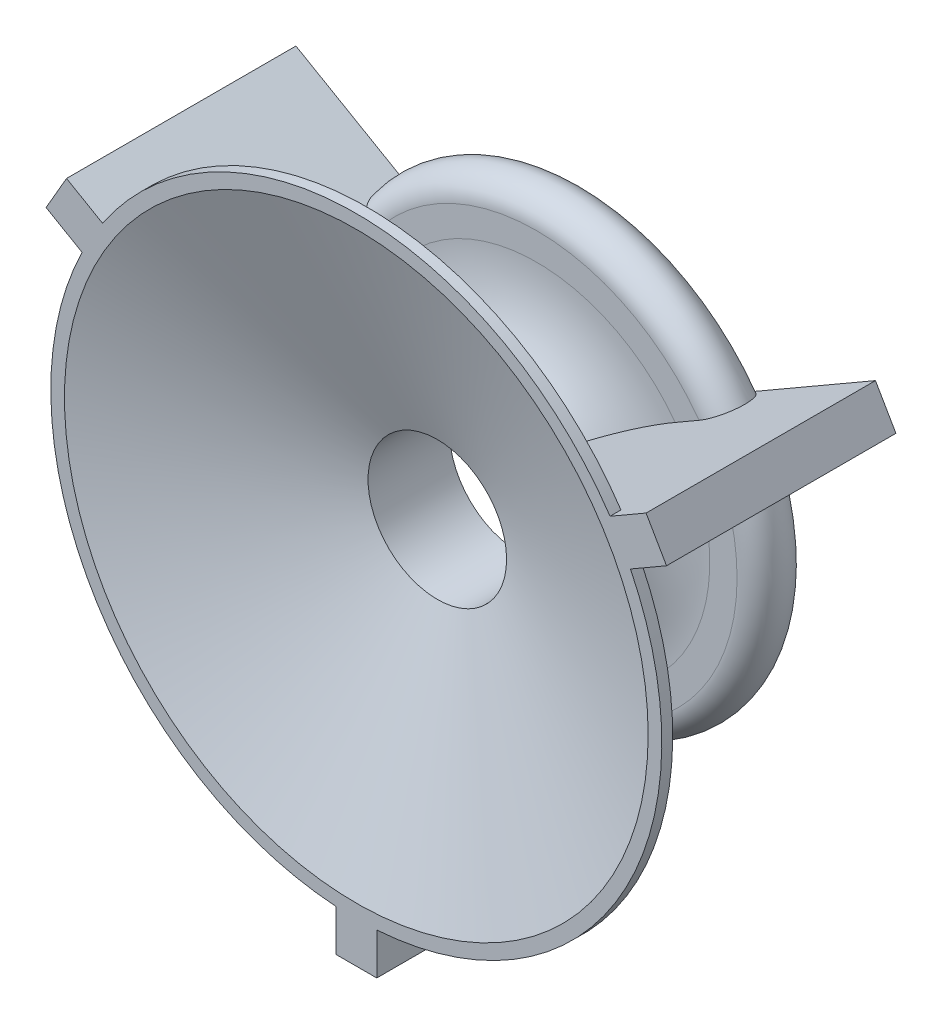
SolidWorks part; units mm, degrees
material "AA356.0-F"
ref_plane "Front Plane" through (0, 0, 0) normal (1, 0, 0) x (0, 1, 0)
ref_plane "Top Plane" through (0, 0, 0) normal (0, 0, 1) x (0, 1, 0)
ref_plane "Right Plane" through (0, 0, 0) normal (0, 1, 0) x (-1, 0, 0)
ref_axis "Axis1" through (0, 0, 59.8884) along (0, 0, -1)
sketch "Sketch1" plane through (0, 0, 0) normal (1, 0, 0) x (0, 1, 0)
  line L0 (0, 0) -> (-25.4, 0) construction
  line L1 (-127, 34.7) -> (-107, 34.7)
  line L2 (-107, 34.7) -> (-25.4, 5)
  line L3 (-25.4, 5) -> (-25.4, -20.4)
  line L4 (-63.5, -35.4) -> (-63.5, -45.4) construction
  line L5 (-63.5, -35.4) -> (-73.5, -35.4)
  line L6 (-73.5, -35.4) -> (-73.5, -45.4) construction
  line L7 (-73.5, -45.4) -> (-63.5, -45.4)
  line L8 (-63.5, -45.4) -> (-63.5, -49.4)
  line L9 (-63.5, -49.4) -> (-73.5, -49.4)
  line L10 (-73.5, -31.4) -> (-63.5, -31.4)
  line L11 (-30.4, -19.4711) -> (-30.4, 2.5631)
  line L12 (-30.4, 2.5631) -> (-107.7053, 30.7)
  line L13 (-107.7053, 30.7) -> (-127, 30.7)
  line L14 (-127, 30.7) -> (-127, 34.7)
  line L15 (-25.4, -20.4) -> (-25.4, -24.9)
  line L16 (-127, 30.7) -> (-127, -49.4)
  line L17 (-127, -49.4) -> (-73.5, -49.4)
  line L18 (-25.4, -24.9) -> (-30.8905, -24.9)
  line L23 (-112, 34.7) -> (-112, 30.7)
  arc A0 (-25.4, -20.4) -> (-63.5, -35.4) centre (-63.5, 20.487) cw
  arc A1 (-73.5, -35.4) -> (-73.5, -45.4) centre (-73.5, -40.4) ccw
  arc A2 (-73.5, -49.4) -> (-73.5, -31.4) centre (-73.5, -40.4) cw
  arc A3 (-63.5, -31.4) -> (-30.4, -19.4711) centre (-63.5, 20.487) ccw
  point P23 (-25.4, -7.7)
  dimension "D1" = 5
  dimension "D2" = 127
  dimension "D3" = 25.4
  dimension "D4" = 20
  dimension "D5" = 15
  dimension "D6" = 4
  dimension "D7" = 5
  dimension "D8" = 25.4
  dimension "D9" = 4
  dimension "D10" = 63.5
  dimension "D11" = 10
  dimension "D12" = 10
  dimension "D13" = 4
  dimension "D14" = 15
  dimension "D15" = 5
  dimension "D16" = 10.5
revolve "Revolve1" add sketch "Sketch1" angle 360 about axis through (0, 0, 59.8884) along (0, 0, -1) region at (0, -109.5, 33.4928) region at (0, -27.1901, -23.4323)
extrude "Boss-Extrude2" add sketch "Sketch1<4>" along normal blind 7.5 and the other way blind 7.5 contours L10 A3 L11 L12 L13 L16 L17 A2 | A3 L10 L5 A0 L3 L2 L1 L23 L13 L12 L11 | L23 L1 L14 L13 | A2 A1 | L7 L9 L8 region at (0, -119.5, 32.7) region at (0, -109.5, 33.4928) region at (0, -87.6747, -9.8836)
sketch "Sketch1<4>" plane through (0, 0, 0) normal (1, 0, 0) x (0, 1, 0) same geometry as "Sketch1"
pattern_circular "CirPattern1" count 3 over 360 about axis through (0, 0, 59.8884) along (0, 0, -1) of "Boss-Extrude2"
